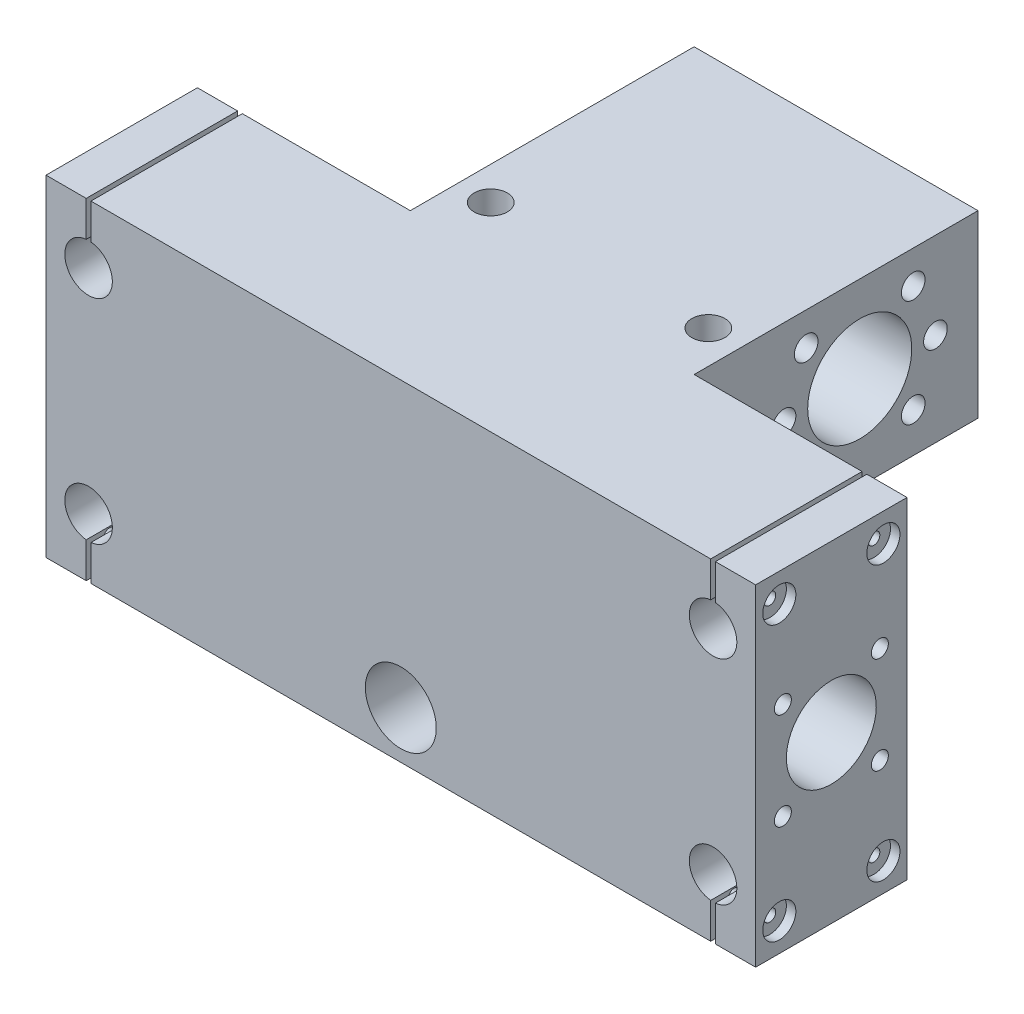
SolidWorks part; units mm, degrees
material "1060 Alloy"
ref_plane "Front Plane" through (0, 0, 0) normal (0, 0, 1) x (1, 0, 0)
ref_plane "Top Plane" through (0, 0, 0) normal (0, 1, 0) x (1, 0, 0)
ref_plane "Right Plane" through (0, 0, 0) normal (1, 0, 0) x (0, 0, -1)
sketch "Sketch1" plane through (0, 0, 0) normal (0, 0, 1) x (1, 0, 0)
  line L1 (-150, 0) -> (0, 0)
  line L2 (-150, 0) -> (-150, -70)
  line L3 (-150, -70) -> (0, -70)
  line L4 (0, 0) -> (0, -70)
  dimension "D1" = 150
  dimension "D2" = 70
extrude "Boss-Extrude1" add sketch "Sketch1" along normal blind 32
sketch "Sketch2" plane through (-150, 0, 0) normal (-1, 0, 0) x (0, 0, 1)
  line L0 (16, 0) -> (16, -70) construction
  line L1 (32, 0) -> (0, 0) construction
  line L2 (32, -70) -> (0, -70) construction
  line L3 (0, -35) -> (32, -35) construction
  line L4 (0, 0) -> (0, -70) construction
  line L5 (32, 0) -> (32, -70) construction
  circle A0 centre (16, -35) radius 9.5
  dimension "D1" = 19
extrude "Linear_bearing-cut-1" cut sketch "Sketch2" against normal blind 55
sketch "Sketch5" plane through (0, 0, 32) normal (0, 0, 1) x (1, 0, 0)
  line L0 (-75, 0) -> (-75, -70) construction
  line L1 (0, 0) -> (-150, 0) construction
  line L2 (-150, -70) -> (0, -70) construction
  line L3 (0, -35) -> (-150, -35) construction
  line L4 (0, -70) -> (0, 0) construction
  line L5 (-150, 0) -> (-150, -70) construction
  line L6 (-141, 0) -> (-141, -12.5) construction
  line L7 (-141, -12.5) -> (-9, -12.5) construction
  line L8 (-9, -12.5) -> (-9, 0) construction
  line L9 (-9, -57.5) -> (-9, -70) construction
  line L10 (-141, -57.5) -> (-9, -57.5) construction
  line L11 (-141, -70) -> (-141, -57.5) construction
  line L12 (-141.5, 0) -> (-141.5, -7.5)
  line L13 (-140.5, 0) -> (-140.5, -7.5)
  line L14 (-8.5, 0) -> (-8.5, -7.5)
  line L15 (-9.5, 0) -> (-9.5, -7.5)
  line L16 (-141.5, -70) -> (-141.5, -62.5)
  line L17 (-140.5, -70) -> (-140.5, -62.5)
  line L18 (-9.5, -70) -> (-9.5, -62.5)
  line L19 (-8.5, -70) -> (-8.5, -62.5)
  line L20 (-141.5, 0) -> (-140.5, 0)
  line L21 (-9.5, 0) -> (-8.5, 0)
  line L22 (-9.5, -70) -> (-8.5, -70)
  line L23 (-141.5, -70) -> (-140.5, -70)
  arc A0 (-141.5, -7.5) -> (-140.5, -7.5) centre (-141, -12.5) ccw
  arc A1 (-8.5, -7.5) -> (-9.5, -7.5) centre (-9, -12.5) cw
  arc A2 (-141.5, -62.5) -> (-140.5, -62.5) centre (-141, -57.5) cw
  arc A3 (-8.5, -62.5) -> (-9.5, -62.5) centre (-9, -57.5) ccw
  dimension "D1" = 9
  dimension "D3" = 12.5
  dimension "D5" = 0.5
  dimension "D6" = 7.5
extrude "Y-axis-shafts-cut" cut sketch "Sketch5" against normal through all
sketch "Sketch6" plane through (-95, 0, 0) normal (-1, 0, 0) x (0, 0, 1)
  line L0 (16, -25.5) -> (16, -44.5) construction
  circle A0 centre (16, -35) radius 9.5 construction
  circle A1 centre (16, -35) radius 9.5 construction
  circle A2 centre (16, -35) radius 6
  dimension "D1" = 12
sketch "Sketch7" plane through (0, 0, 0) normal (1, 0, 0) x (0, 0, -1)
  circle A0 centre (-16, -35) radius 9.5
  dimension "D1" = 19
extrude "Linear-bearing-cut-2" cut sketch "Sketch7" against normal blind 55
extrude "between-bearings" cut sketch "Sketch6" against normal through all
sketch "Sketch8" plane through (-150, 0, 0) normal (-1, 0, 0) x (0, 0, 1)
  line L0 (5, 0) -> (5, -6) construction
  line L1 (32, 0) -> (0, 0) construction
  line L2 (5, -6) -> (27, -6) construction
  line L3 (27, -6) -> (27, 0) construction
  line L4 (0, 0) -> (0, -70) construction
  line L5 (32, 0) -> (32, -70) construction
  line L6 (16, 0) -> (16, -70) construction
  line L7 (32, -70) -> (0, -70) construction
  line L8 (0, -35) -> (32, -35) construction
  line L9 (5, -39.9148) -> (4.7174, -39.9148) construction
  circle A0 centre (5, -6) radius 3.5
  circle A1 centre (27, -6) radius 3.5
  circle A2 centre (27, -64) radius 3.5
  circle A3 centre (5, -64) radius 3.5
  dimension "D4" = 7
  dimension "D1" = 5
  dimension "D3" = 6
extrude "shaft-holder-screw-cut" cut sketch "Sketch8" against normal blind 4
sketch "Sketch9" plane through (-146, 0, 0) normal (-1, 0, 0) x (0, 0, 1)
  line L0 (5, -2.5) -> (5, -9.5) construction
  line L1 (27, -2.5) -> (27, -9.5) construction
  line L2 (27, -60.5) -> (27, -67.5) construction
  line L3 (5, -60.5) -> (5, -67.5) construction
  circle A0 centre (5, -6) radius 3.5 construction
  circle A1 centre (5, -6) radius 3.5 construction
  circle A2 centre (27, -6) radius 3.5 construction
  circle A3 centre (27, -6) radius 3.5 construction
  circle A4 centre (27, -64) radius 3.5 construction
  circle A5 centre (27, -64) radius 3.5 construction
  circle A6 centre (5, -64) radius 3.5 construction
  circle A7 centre (5, -64) radius 3.5 construction
  circle A8 centre (5, -6) radius 1.25
  circle A9 centre (27, -6) radius 1.25
  circle A10 centre (5, -64) radius 1.25
  circle A11 centre (27, -64) radius 1.25
  dimension "D1" = 2.5
extrude "shaft-holder-screw-cut2" cut sketch "Sketch9" against normal blind 20
sketch "Sketch10" plane through (0, 0, 0) normal (1, 0, 0) x (0, 0, -1)
  line L0 (-27, 0) -> (-27, -6) construction
  line L1 (-32, 0) -> (0, 0) construction
  line L2 (-27, -6) -> (-5, -6) construction
  line L3 (-5, -6) -> (-5, 0) construction
  line L4 (-32, -70) -> (-32, 0) construction
  line L5 (0, -70) -> (0, 0) construction
  line L6 (-16, 0) -> (-16, -70) construction
  line L7 (-32, -70) -> (0, -70) construction
  line L8 (-32, -35) -> (0, -35) construction
  circle A0 centre (-27, -6) radius 3.5
  circle A1 centre (-5, -6) radius 3.5
  circle A2 centre (-5, -64) radius 3.5
  circle A3 centre (-27, -64) radius 3.5
  dimension "D4" = 7
  dimension "D1" = 5
  dimension "D2" = 6
extrude "shaft-holder-screw-cut-3" cut sketch "Sketch10" against normal blind 2
sketch "Sketch11" plane through (-2, 0, 0) normal (1, 0, 0) x (0, 0, -1)
  line L0 (-27, -2.5) -> (-27, -9.5) construction
  line L1 (-5, -2.5) -> (-5, -9.5) construction
  line L2 (-5, -60.5) -> (-5, -67.5) construction
  line L3 (-27, -60.5) -> (-27, -67.5) construction
  circle A0 centre (-27, -6) radius 3.5 construction
  circle A1 centre (-27, -6) radius 3.5 construction
  circle A2 centre (-5, -6) radius 3.5 construction
  circle A3 centre (-5, -6) radius 3.5 construction
  circle A4 centre (-5, -64) radius 3.5 construction
  circle A5 centre (-5, -64) radius 3.5 construction
  circle A6 centre (-27, -64) radius 3.5 construction
  circle A7 centre (-27, -64) radius 3.5 construction
  circle A8 centre (-27, -6) radius 1.25
  circle A9 centre (-5, -6) radius 1.25
  circle A10 centre (-5, -64) radius 1.25
  circle A11 centre (-27, -64) radius 1.25
  dimension "D1" = 2.5
extrude "shaft-holder-screw-cut-4" cut sketch "Sketch11" against normal blind 20
sketch "Sketch12" plane through (0, 0, 0) normal (1, 0, 0) x (0, 0, -1)
  line L0 (-5.75, 0) -> (-5.75, -24.75) construction
  line L1 (-32, 0) -> (0, 0) construction
  line L2 (-5.75, -24.75) -> (0, -24.75) construction
  line L3 (0, -70) -> (0, 0) construction
  line L4 (-16, 0) -> (-16, -70) construction
  line L5 (-32, -70) -> (0, -70) construction
  line L6 (0, -35) -> (-32, -35) construction
  line L7 (-32, -70) -> (-32, 0) construction
  circle A0 centre (-5.75, -24.75) radius 1.8
  circle A1 centre (-26.25, -24.75) radius 1.8
  circle A2 centre (-5.75, -45.25) radius 1.8
  circle A3 centre (-26.25, -45.25) radius 1.8
  dimension "D3" = 3.6
  dimension "D1" = 5.75
  dimension "D2" = 24.75
extrude "Linear-bearing-srew1" cut sketch "Sketch12" against normal blind 14
sketch "Sketch13" plane through (-150, 0, 0) normal (-1, 0, 0) x (0, 0, 1)
  line L0 (27.5, 0) -> (27.5, -24.75) construction
  line L1 (32, 0) -> (0, 0) construction
  line L2 (27.5, -24.75) -> (32, -24.75) construction
  line L3 (32, 0) -> (32, -70) construction
  line L4 (16, 0) -> (16, -70) construction
  line L5 (32, -70) -> (0, -70) construction
  line L6 (32, -35) -> (0, -35) construction
  line L7 (0, 0) -> (0, -70) construction
  circle A0 centre (27.5, -24.75) radius 1.85
  circle A1 centre (4.5, -24.75) radius 1.85
  circle A2 centre (27.5, -45.25) radius 1.85
  circle A3 centre (4.5, -45.25) radius 1.85
  dimension "D3" = 3.7
  dimension "D1" = 24.75
  dimension "D2" = 4.5
extrude "Linear-bearing-screw2" cut sketch "Sketch13" against normal blind 14
sketch "Sketch14" plane through (0, 0, 0) normal (0, 0, -1) x (-1, 0, 0)
  line L0 (140.5, -70) -> (9.5, -70) construction
  line L1 (0, -70) -> (0, 0) construction
  circle A0 centre (75, -60) radius 7.5
  dimension "D3" = 15
  dimension "D1" = 10
  dimension "D2" = 75
extrude "Cut-Extrude1" cut sketch "Sketch14" against normal through all
sketch "Sketch15" plane through (0, 0, 0) normal (0, 0, -1) x (-1, 0, 0)
  line L0 (9.5, 0) -> (140.5, 0) construction
  line L1 (45, 0) -> (105, 0)
  line L2 (45, 0) -> (45, -38)
  line L3 (45, -38) -> (105, -38)
  line L4 (105, 0) -> (105, -38)
  line L5 (75, -70) -> (75, 0) construction
  line L6 (140.5, -70) -> (9.5, -70) construction
  point P10 (75, 0)
  dimension "D1" = 38
  dimension "D2" = 60
extrude "Boss-Extrude2" add sketch "Sketch15" along normal blind 60
sketch "Sketch16" plane through (-105, 0, 0) normal (-1, 0, 0) x (0, 0, 1)
  line L1 (-60, -38) -> (0, -38) construction
  line L3 (-60, -38) -> (-60, 0) construction
  circle A0 centre (-35, -18.29) radius 11
  circle A1 centre (-46.3137, -29.6037) radius 2.5
  circle A2 centre (-51, -18.29) radius 2.5
  circle A3 centre (-19, -18.29) radius 2.5
  circle A4 centre (-23.6863, -29.6037) radius 2.5
  circle A5 centre (-23.6863, -6.9763) radius 2.5
  circle A6 centre (-46.3137, -6.9763) radius 2.5
  dimension "D1" = 5
  dimension "D14" = 22
  dimension "D2" = 16
  dimension "D3" = 16
  dimension "D4" = 16
  dimension "D5" = 16
  dimension "D6" = 16
  dimension "D7" = 16
  dimension "D8" = 45
  dimension "D9" = 45
  dimension "D10" = 45
  dimension "D11" = 45
  dimension "D12" = 25
  dimension "D13" = 19.71
extrude "Cut-Extrude2" cut sketch "Sketch16" against normal up to next
sketch "Sketch17" plane through (0, -38, 0) normal (0, -1, 0) x (1, 0, 0)
  line L0 (-45, -60) -> (-105, -60) construction
  line L1 (-105, -60) -> (-105, 0) construction
  line L2 (-45, -60) -> (-45, 0) construction
  circle A0 centre (-98, -10) radius 3.5
  circle A1 centre (-52, -10) radius 3.5
  point P6 (0, 0)
  point P7 (0, 0)
  dimension "D4" = 7
  dimension "D1" = 50
  dimension "D2" = 7
  dimension "D3" = 7
extrude "Cut-Extrude3" cut sketch "Sketch17" against normal up to next
